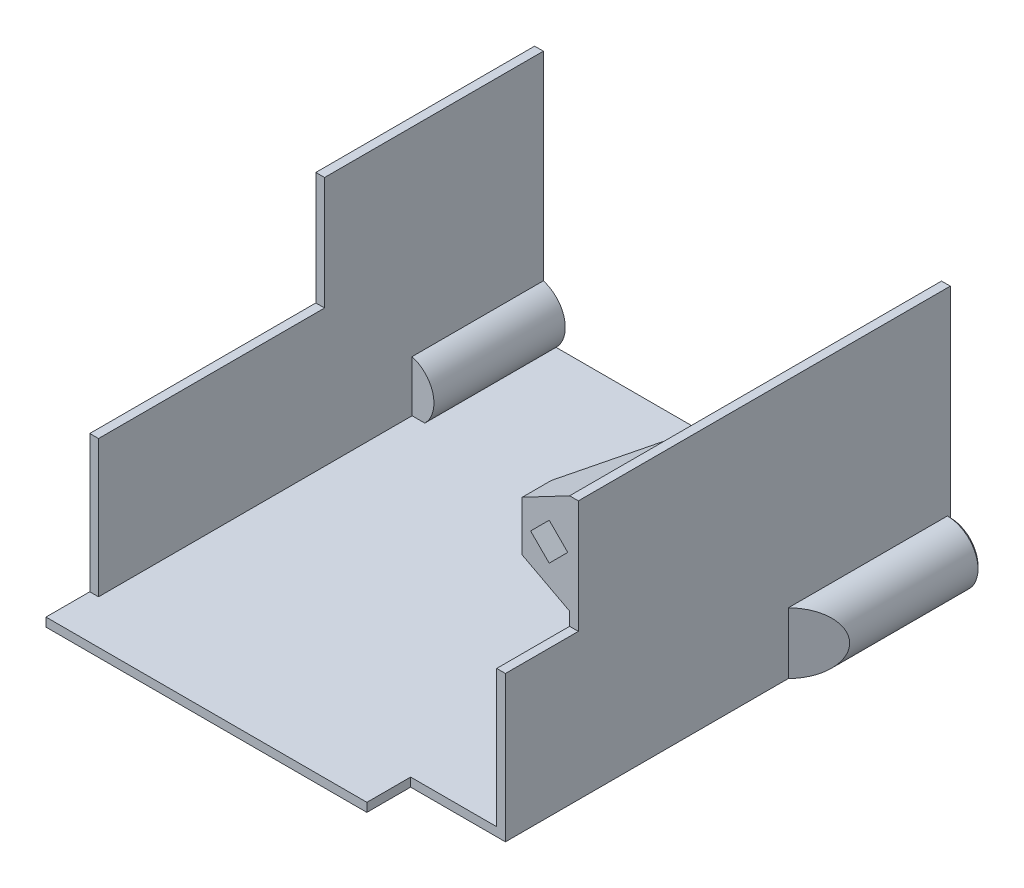
SolidWorks part; units mm, degrees
material "Custom Plastic"
ref_plane "Front Plane" through (0, 0, 0) normal (0, 0, 1) x (1, 0, 0)
ref_plane "Top Plane" through (0, 0, 0) normal (0, 1, 0) x (1, 0, 0)
ref_plane "Right Plane" through (0, 0, 0) normal (1, 0, 0) x (0, 0, -1)
sketch "Sketch1" plane through (0, 0, 0) normal (0, 0, 1) x (1, 0, 0)
  line L1 (-33.6475, 14.5475) -> (-34.8475, 14.5475)
  line L2 (-33.6475, -19.7525) -> (-33.6475, -20.9525) construction
  line L3 (-31.9081, -19.7525) -> (19.2131, -19.7525)
  line L4 (20.9525, 14.5475) -> (20.9525, -12.7276)
  line L5 (-33.6475, -12.7276) -> (-33.6475, 14.5475)
  line L7 (20.9525, 14.5475) -> (22.1525, 14.5475)
  line L8 (-34.8475, 14.5475) -> (-34.8475, -12.5525)
  line L9 (-34.8475, -20.9525) -> (22.1525, -20.9525)
  line L10 (22.1525, 14.5475) -> (22.1525, -12.5525)
  arc A0 (22.1525, -20.9525) -> (22.1525, -12.5525) centre (22.1525, -16.7525) ccw
  circle A1 centre (22.1525, -16.7525) radius 1.6 construction
  arc A2 (20.9525, -12.7276) -> (19.2131, -19.7525) centre (22.1525, -16.7525) ccw
  circle A3 centre (-34.8475, -16.7525) radius 1.6 construction
  arc A4 (-34.8475, -12.5525) -> (-34.8475, -20.9525) centre (-34.8475, -16.7525) ccw
  arc A6 (-31.9081, -19.7525) -> (-33.6475, -12.7276) centre (-34.8475, -16.7525) ccw
  dimension "D2" = 3.2
  dimension "D5" = 4.2
  dimension "D1" = 1.2
  dimension "D3" = 57
  dimension "D4" = 35.5
extrude "Boss-Extrude1" add sketch "Sketch1" along normal blind 67
sketch "Sketch2" plane through (0, 0, 67) normal (0, 0, 1) x (1, 0, 0)
  line L0 (-34.8475, -20.9525) -> (22.1525, -20.9525) construction
  line L1 (9.1525, -20.9525) -> (32.8781, -20.9525)
  line L2 (9.1525, -20.9525) -> (9.1525, -19.7525)
  line L3 (-34.8475, 12.6741) -> (32.8781, 12.6741)
  line L4 (32.8781, -20.9525) -> (32.8781, 12.6741)
  line L5 (22.1525, -12.5525) -> (22.1525, 14.5475) construction
  line L6 (9.1525, -19.7525) -> (-34.8475, -19.7525)
  line L7 (19.2131, -19.7525) -> (-31.9081, -19.7525) construction
  line L8 (-34.8475, 14.5475) -> (-34.8475, -12.5525) construction
  line L9 (-34.8475, -20.9525) -> (-34.8475, -19.7525)
  line L10 (-34.8475, -20.9525) -> (-42.7406, -20.9525)
  line L11 (-34.8475, -20.9525) -> (22.1525, -20.9525) construction
  line L12 (-42.7406, -20.9525) -> (-42.7406, -7.5075)
  line L13 (-42.7406, -7.5075) -> (-34.8475, -7.5075)
  line L14 (-34.8475, -7.5075) -> (-34.8475, 12.6741)
  dimension "D1" = 13
extrude "Cut-Extrude1" cut sketch "Sketch2" against normal blind 6
sketch "Sketch3" plane through (0, 0, 61) normal (0, 0, 1) x (1, 0, 0)
  line L0 (22.1525, -12.5525) -> (22.1525, 12.6741) construction
  line L1 (-34.8475, 14.5475) -> (22.1525, 14.5475)
  line L2 (-34.8475, 14.5475) -> (-34.8475, -0.9525)
  line L3 (-34.8475, -0.9525) -> (22.1525, -0.9525)
  line L4 (22.1525, 14.5475) -> (22.1525, -0.9525)
  dimension "D1" = 15.5
extrude "Cut-Extrude2" cut sketch "Sketch3" against normal blind 10 and the other way blind 10
sketch "Sketch4" plane through (0, 0, 51) normal (0, 0, 1) x (1, 0, 0)
  line L0 (-34.8475, 14.5475) -> (-34.8475, -0.9525) construction
  line L1 (-34.8475, 14.5475) -> (-33.6475, 14.5475)
  line L2 (-34.8475, 14.5475) -> (-34.8475, -0.9525)
  line L3 (-34.8475, -0.9525) -> (-33.6475, -0.9525)
  line L4 (-33.6475, 14.5475) -> (-33.6475, -0.9525)
extrude "Cut-Extrude3" cut sketch "Sketch4" against normal blind 21
sketch "Sketch6" plane through (0, 0, 0) normal (0, 0, -1) x (-1, 0, 0)
  circle A0 centre (-22.1525, -16.7525) radius 1.6
  circle A1 centre (34.8475, -16.7525) radius 1.6
  arc A2 (34.8475, -20.9525) -> (34.8475, -12.5525) centre (34.8475, -16.7525) ccw construction
  arc A3 (-22.1525, -12.5525) -> (-22.1525, -20.9525) centre (-22.1525, -16.7525) ccw construction
  dimension "D1" = 3.2
extrude "Cut-Extrude4" cut sketch "Sketch6" against normal blind 16
sketch "Sketch7" plane through (0, 0, 61) normal (0, 0, 1) x (1, 0, 0)
  line L0 (19.2131, -19.7525) -> (9.1525, -19.7525) construction
  line L1 (22.1525, -12.5525) -> (31.8181, -12.5525)
  line L2 (22.1525, -12.5525) -> (22.1525, -20.9525)
  line L3 (22.1525, -20.9525) -> (31.8181, -20.9525)
  line L4 (31.8181, -12.5525) -> (31.8181, -20.9525)
  line L5 (20.9525, -12.7276) -> (15.0843, -12.7276)
  line L6 (20.9525, -12.7276) -> (20.9525, -19.7525)
  line L7 (20.9525, -19.7525) -> (15.0843, -19.7525)
  line L8 (15.0843, -12.7276) -> (15.0843, -19.7525)
  line L9 (-33.6475, -12.7276) -> (-33.6475, -0.9525) construction
  line L10 (-34.8475, -20.9525) -> (-44.0251, -20.9525)
  line L11 (-34.8475, -20.9525) -> (-34.8475, -7.6032)
  line L12 (-34.8475, -7.6032) -> (-44.0251, -7.6032)
  line L13 (-44.0251, -20.9525) -> (-44.0251, -7.6032)
  line L14 (-33.6475, -7.6032) -> (-26.816, -7.6032)
  line L15 (-33.6475, -7.6032) -> (-33.6475, -19.7525)
  line L16 (-33.6475, -19.7525) -> (-26.816, -19.7525)
  line L17 (-26.816, -7.6032) -> (-26.816, -19.7525)
  line L18 (9.1525, -19.7525) -> (-34.8475, -19.7525) construction
extrude "Cut-Extrude5" cut sketch "Sketch7" against normal offset from surface (43 mm away) 18 up to face at (-36.4475, -16.7525, 0)
chamfer "Chamfer1" distance 4.2 angle 45 2 edges at (22.1525, -16.7525, 18) (-34.8475, -16.7525, 18)
chamfer "Chamfer3" distance 0.6 angle 30 2 edges at (20.5525, -16.7525, 0) (-36.4475, -16.7525, 0) first distance on face at (20.5525, -16.7525, 16) first distance on face at (-36.4475, -16.7525, 16)
chamfer "Chamfer4" distance 0.4 angle 45 3 edges at (-39.0475, -16.7525, 0) (-6.3475, -20.9525, 0) (26.3525, -16.7525, 0)
sketch "Sketch8" plane through (0, 0, 51) normal (0, 0, 1) x (1, 0, 0)
  line L0 (18.1525, 9.2975) -> (14.4525, 9.2975) construction
  line L1 (15.6025, 7.6975) -> (18.1525, 10.2475)
  line L2 (14.4525, 6.0975) -> (18.1525, 6.0975) construction
  line L4 (14.4525, 11.1225) -> (14.4525, 9.2975)
  line L5 (14.4525, 6.0975) -> (14.4525, 4.2725)
  line L7 (20.9525, 14.5475) -> (20.9525, -0.9525) construction
  line L8 (20.9525, 0.8475) -> (22.1525, 0.8475)
  line L9 (22.1525, -0.9525) -> (22.1525, 14.5475) construction
  line L10 (22.1525, 0.8475) -> (22.1525, 14.5475)
  line L11 (22.1525, 14.5475) -> (20.9525, 14.5475)
  line L12 (15.6025, 7.6975) -> (18.1525, 5.1475)
  line L13 (18.1525, 10.2475) -> (20.7025, 7.6975)
  line L14 (18.1525, 5.1475) -> (20.7025, 7.6975)
  line L15 (15.6025, 7.6975) -> (20.7025, 7.6975) construction
  line L16 (18.1525, 10.2475) -> (18.1525, 5.1475) construction
  line L17 (14.4525, 9.2975) -> (14.4525, 6.0975)
  line L18 (20.9525, 14.5475) -> (14.4525, 11.1225)
  line L19 (20.9525, 0.8475) -> (14.4525, 4.2725)
  arc A0 (18.1525, 6.0975) -> (18.1525, 9.2975) centre (18.1525, 7.6975) ccw construction
  circle A1 centre (18.1525, 7.6975) radius 2.55 construction
  dimension "D1" = 1.6
  dimension "D5" = 5.1
  dimension "D2" = 2.8
  dimension "D3" = 6.85
  dimension "D4" = 6.5
  dimension "D6" = 6.85
extrude "Boss-Extrude2" add sketch "Sketch8" against normal blind 13
sketch "Sketch10" plane through (0, 0, 38) normal (0, 0, -1) x (-1, 0, 0)
  line L0 (-18.1525, 10.6975) -> (-14.4525, 10.6975)
  line L1 (-14.4525, 11.1225) -> (-14.4525, 4.2725) construction
  line L2 (-14.4525, 10.6975) -> (-14.4525, 4.6975)
  line L3 (-14.4525, 4.6975) -> (-18.1525, 4.6975)
  line L5 (-18.1525, 10.2475) -> (-18.1525, 5.1475) construction
  arc A0 (-18.1525, 10.6975) -> (-18.1525, 4.6975) centre (-18.1525, 7.6975) ccw
  arc A1 (-18.1525, 4.6975) -> (-18.1525, 10.6975) centre (-18.1525, 7.6975) ccw construction
  dimension "D1" = 3
extrude "Cut-Extrude6" cut sketch "Sketch10" against normal offset from surface 6 and the other way blind 10 up to face at (19.4382, 6.2046, 51)
sketch "Sketch11" plane through (0, 14.5475, 0) normal (0, 1, 0) x (1, 0, 0)
  line L0 (20.9525, -38) -> (14.4525, -47)
  line L1 (14.4525, -38) -> (14.4525, -51) construction
  line L2 (14.4525, -47) -> (14.4525, -38)
  line L3 (14.4525, -38) -> (20.9525, -38)
extrude "Cut-Extrude7" cut sketch "Sketch11" against normal up to surface (10.275 mm away) up to face at (17.7025, 2.56, 44.5)
